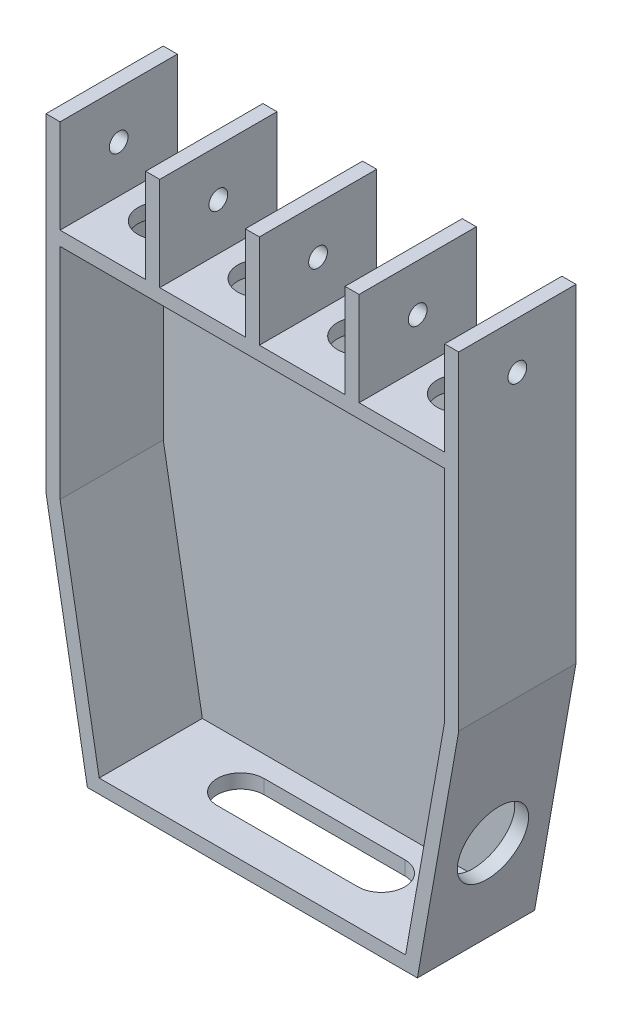
SolidWorks part; units mm, degrees
ref_plane "Front Plane" through (0, 0, 0) normal (0, 0, 1) x (1, 0, 0)
ref_plane "Top Plane" through (0, 0, 0) normal (0, 1, 0) x (1, 0, 0)
ref_plane "Right Plane" through (0, 0, 0) normal (1, 0, 0) x (0, 0, -1)
sketch "Sketch1" plane through (0, 0, 0) normal (0, 0, 1) x (1, 0, 0)
  line L0 (213.3333, 360) -> (1066.6667, 360) construction
sketch "Sketch2" plane through (0, 0, 0) normal (0, 0, 1) x (1, 0, 0)
  line L6 (-8.3336, 94) -> (73.6664, 94)
  line L7 (73.6664, 94) -> (73.6664, 47.2625)
  line L8 (73.6664, 47.2625) -> (65.3327, 0)
  line L9 (65.3327, 0) -> (0, 0)
  line L10 (0, 0) -> (-8.3336, 47.2625)
  line L11 (-8.3336, 47.2625) -> (-8.3336, 94)
  line L12 (-11.3336, 97) -> (76.6664, 97)
  line L13 (76.6664, 97) -> (76.6664, 47)
  line L14 (76.6664, 47) -> (67.85, -3)
  line L15 (67.85, -3) -> (-2.5173, -3)
  line L16 (-2.5173, -3) -> (-11.3336, 47)
  line L17 (-11.3336, 47) -> (-11.3336, 97)
  dimension "D1" = 100
  dimension "D2" = 100
  dimension "D4" = 88
  dimension "D5" = 100
  dimension "D6" = 50
  dimension "D3" = 3
extrude "Boss-Extrude2" add sketch "Sketch2" along normal blind 3 contours L17 L16 L15 L14 L13 L12 L10 L11 L6 L7 L8 L9 | L11 L10 L9 L8 L7 L6 region at (32.6664, 48.6826, 0) region at (32.6664, 95.6679, 0)
extrude "Boss-Extrude3" add sketch "Sketch2<4>" along normal blind 25
sketch "Sketch2<4>" plane through (0, 0, 0) normal (0, 0, 1) x (1, 0, 0) same geometry as "Sketch2"
sketch "Sketch3" plane through (0, 0, 0) normal (0, 0, -1) x (-1, 0, 0)
  line L0 (11.3336, 97) -> (11.3336, 117)
  line L1 (11.3336, 117) -> (8.3336, 117)
  line L2 (8.3336, 117) -> (8.3336, 97)
  line L3 (11.3336, 97) -> (-76.6664, 97) construction
  line L4 (8.3336, 97) -> (11.3336, 97)
  line L5 (-12.9164, 97) -> (-9.9164, 97)
  line L6 (-9.9164, 97) -> (-9.9164, 117)
  line L7 (-9.9164, 117) -> (-12.9164, 117)
  line L8 (-12.9164, 117) -> (-12.9164, 97)
  line L9 (-34.1664, 97) -> (-31.1664, 97)
  line L10 (-31.1664, 97) -> (-31.1664, 117)
  line L11 (-31.1664, 117) -> (-34.1664, 117)
  line L12 (-34.1664, 117) -> (-34.1664, 97)
  line L13 (-55.4164, 97) -> (-52.4164, 97)
  line L14 (-52.4164, 97) -> (-52.4164, 117)
  line L15 (-52.4164, 117) -> (-55.4164, 117)
  line L16 (-55.4164, 117) -> (-55.4164, 97)
  line L17 (-76.6664, 97) -> (-73.6664, 97)
  line L18 (-73.6664, 97) -> (-73.6664, 117)
  line L19 (-73.6664, 117) -> (-76.6664, 117)
  line L20 (-76.6664, 117) -> (-76.6664, 97)
  line L21 (8.3336, 97) -> (-12.9164, 97) construction
  line L22 (-76.6664, 97) -> (-76.6664, 47) construction
  dimension "D1" = 20
  dimension "D2" = 3
  dimension "D4" = 21.25
  dimension "D3" = 5
extrude "Boss-Extrude4" add sketch "Sketch3" against normal up to surface (25 mm away) up to face at (32.6664, 47, 25)
sketch "Sketch4" plane through (66.3171, -11.6935, 0) normal (0.9848, -0.1736, 0) x (0, 0, -1)
  line L0 (-25, 8.8276) -> (0, 8.8276) construction
  line L1 (0, 59.5989) -> (0, 8.8276) construction
  circle A0 centre (-12.5, 29.6308) radius 7.5
  dimension "D1" = 15
  dimension "D3" = 12.5
  dimension "D2" = 20.8032
extrude "Cut-Extrude1" cut sketch "Sketch4" against normal blind 6
sketch "Sketch5" plane through (0, -3, 0) normal (0, -1, 0) x (1, 0, 0)
  line L0 (47.6664, 12.5) -> (17.6664, 12.5) construction
  line L1 (47.6664, 7.5) -> (17.6664, 7.5)
  line L2 (47.6664, 17.5) -> (17.6664, 17.5)
  line L3 (-2.5173, 0) -> (67.85, 0) construction
  line L4 (67.85, 25) -> (67.85, 0) construction
  arc A0 (47.6664, 7.5) -> (47.6664, 17.5) centre (47.6664, 12.5) ccw
  arc A1 (17.6664, 17.5) -> (17.6664, 7.5) centre (17.6664, 12.5) ccw
  point P2 (32.6664, 12.5)
  point P7 (32.6664, 0)
  point P13 (67.85, 12.5)
  dimension "D2" = 5
  dimension "D1" = 30
extrude "Cut-Extrude2" cut sketch "Sketch5" against normal blind 6
sketch "Sketch6" plane through (0, 97, 0) normal (0, 1, 0) x (1, 0, 0)
  line L0 (9.9164, -25) -> (-8.3336, -25) construction
  line L1 (-8.3336, -25) -> (-8.3336, 0) construction
  line L2 (0.7914, -12.5) -> (22.0414, -12.5) construction
  circle A0 centre (0.7914, -12.5) radius 5
  circle A1 centre (22.0414, -12.5) radius 5
  circle A2 centre (43.2914, -12.5) radius 5
  circle A3 centre (64.5414, -12.5) radius 5
  point P4 (0.7914, -25)
  point P7 (-8.3336, -12.5)
  dimension "D1" = 10
  dimension "D3" = 21.25
  dimension "D2" = 4
extrude "Cut-Extrude3" cut sketch "Sketch6" against normal blind 6
sketch "Sketch7" plane through (-11.3336, 0, 0) normal (-1, 0, 0) x (0, 0, 1)
  line L0 (0, 117) -> (25, 117) construction
  circle A0 centre (12.5, 107) radius 2
  point P7 (12.5, 117)
  dimension "D1" = 4
  dimension "D2" = 10
extrude "Cut-Extrude4" cut sketch "Sketch7" against normal blind 153
